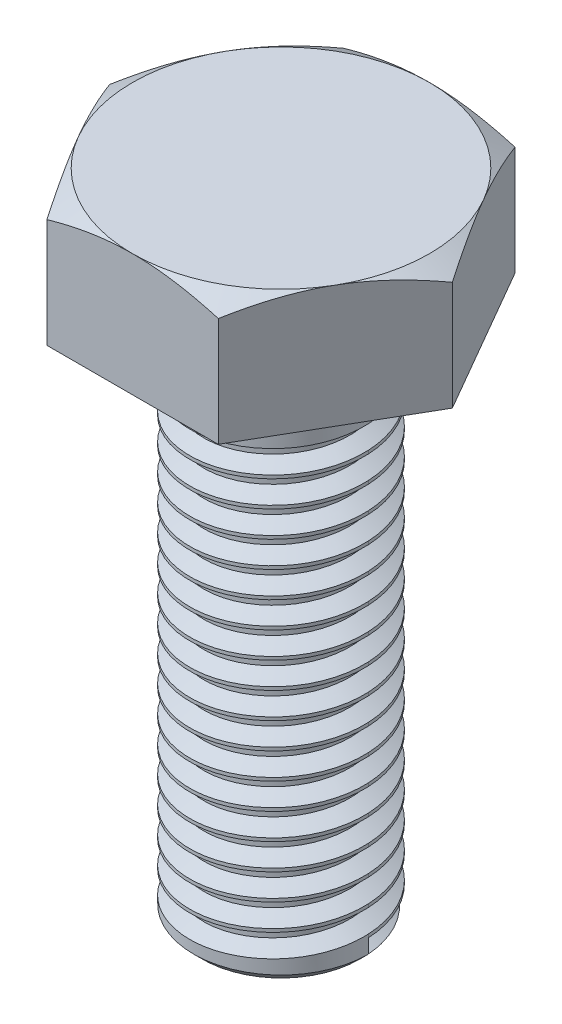
SolidWorks part; units mm, degrees
ref_plane "Ön Düzlem" through (0, 0, 0) normal (0, 0, 1) x (1, 0, 0)
ref_plane "Üst Düzlem" through (0, 0, 0) normal (0, 1, 0) x (1, 0, 0)
ref_plane "Sağ Düzlem" through (0, 0, 0) normal (1, 0, 0) x (0, 0, -1)
sketch "Çizim1" plane through (0, 0, 0) normal (0, 1, 0) x (1, 0, 0)
  line L1 (9.815, 0) -> (4.9075, 8.5)
  line L2 (4.9075, 8.5) -> (-4.9075, 8.5)
  line L3 (-4.9075, 8.5) -> (-9.815, 0)
  line L4 (-9.815, 0) -> (-4.9075, -8.5)
  line L5 (-4.9075, -8.5) -> (4.9075, -8.5)
  line L6 (4.9075, -8.5) -> (9.815, 0)
  circle A0 centre (0, 0) radius 8.5 construction
  dimension "D1" = 17
extrude "Yükseklik-Ekstrüzyon1" add sketch "Çizim1" along normal blind 7
sketch "Çizim2" plane through (0, 7, 0) normal (0, 1, 0) x (1, 0, 0)
  line L0 (-4.9075, 8.5) -> (-9.815, 0) construction
  line L1 (9.815, 0) -> (4.9075, 8.5) construction
  line L2 (-4.9075, -8.5) -> (4.9075, -8.5) construction
  circle A0 centre (0, 0) radius 8.5
extrude "Kes-Ekstrüzyon1" cut sketch "Çizim2" against normal blind 7 draft 60 flip side to cut
sketch "Çizim4" plane through (0, 0, 0) normal (0, -1, 0) x (1, 0, 0)
  circle A0 centre (0, 0) radius 5
  dimension "D1" = 10
extrude "Yükseklik-Ekstrüzyon2" add sketch "Çizim4" along normal blind 30
thread "Diş1" pitch 1.5 method cut profile "Diş Profili1" start angle 0, offset 0, length 26, pitch 1.5, diameter 10
ref_plane "Düzlem1" through (5, -30, 0) normal (0, 0, 1) x (1, 0, 0)
sketch "Diş Profili1" plane through (5, -30, 0) normal (0, 0, 1) x (1, 0, 0)
  line L0 (0, 0) -> (0, 1.5) construction
  line L11 (0, 0) -> (0, 1.3125)
  line L12 (0, 1.3125) -> (-0.8119, 0.8437)
  line L13 (-0.8119, 0.8437) -> (-0.8119, 0.4687)
  line L15 (-0.8119, 0.4687) -> (0, 0)
  line L17 (-0.8119, 0.6562) -> (0, 0.6562) construction
  point P2 (0, 0)
  dimension "Pitch" = 1.5
  dimension "Profile_Angle" = 60
  dimension "Profile_Land" = 0.375
  dimension "Profile_Height" = 0.8119
chamfer "Pah1" distance 0.5 angle 45 1 edges at (0, -30, -5)
